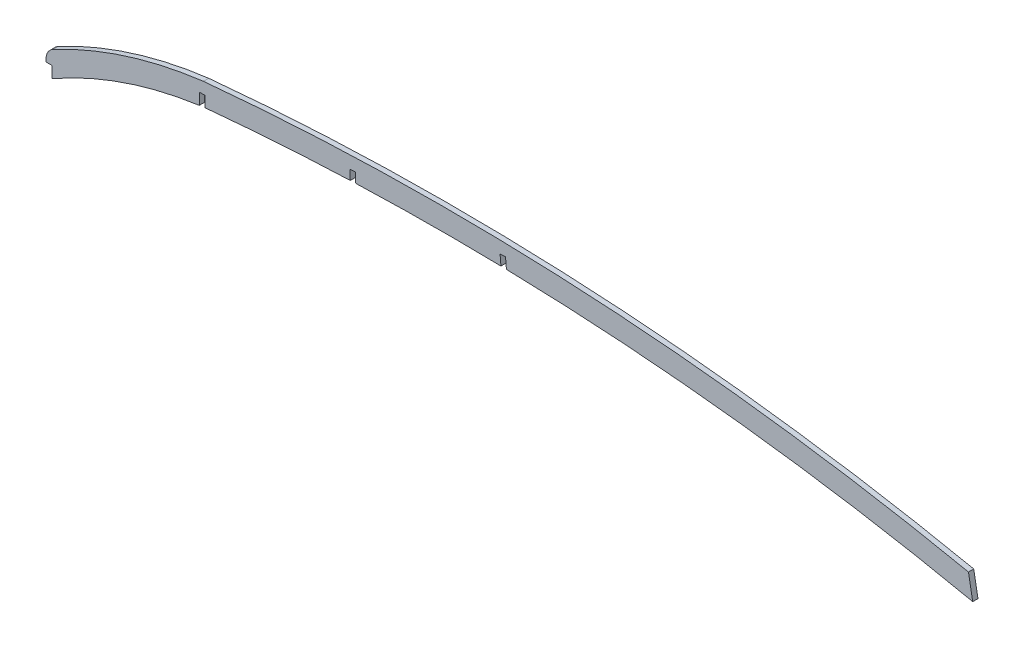
SolidWorks part; units mm, degrees
material "Balsa"
ref_plane "Front Plane" through (0, 0, 0) normal (0, 0, 1) x (1, 0, 0)
ref_plane "Top Plane" through (0, 0, 0) normal (0, 1, 0) x (1, 0, 0)
ref_plane "Right Plane" through (0, 0, 0) normal (1, 0, 0) x (0, 0, -1)
sketch "Sketch1" plane through (0, 0, 0) normal (0, 0, 1) x (1, 0, 0)
  line L0 (0, 101.6) -> (0, 100.0553)
  line L1 (0, -1.7463) -> (0, 1.7463) construction
  line L2 (0, 86.36) -> (8.1082, 86.36) construction
  line L3 (3.7499, 106.3536) -> (3.7499, -82.5359) construction
  line L4 (8.1082, 101.6) -> (0, 101.6) construction
  line L5 (92.329, 130.518) -> (92.329, 123.5672)
  line L6 (3.7499, 93.1973) -> (0, 91.0322) construction
  line L7 (0, 99.5163) -> (0, 88.039) construction
  line L8 (558.2295, 97.6273) -> (555.6382, 111.8229)
  line L9 (0, 91.0322) -> (0, 86.36) construction
  line L10 (3.7499, 93.1973) -> (3.7499, 100.0553)
  line L11 (3.7499, 100.0553) -> (0, 97.8902) construction
  line L12 (0, 97.8902) -> (0, 91.0322) construction
  line L13 (3.7499, 100.0553) -> (0, 100.0553)
  line L14 (0, 100.0553) -> (0, 97.8902) construction
  line L17 (92.3925, 137.6297) -> (92.3925, -54.5591) construction
  line L18 (95.631, 130.518) -> (95.631, 124.0109)
  line L19 (95.5675, -54.5591) -> (95.5675, 137.6297) construction
  line L20 (95.5675, 137.6297) -> (92.3925, 137.6297) construction
  line L21 (93.98, 137.6297) -> (93.98, 130.518) construction
  line L22 (92.329, 130.518) -> (95.631, 130.518)
  line L23 (92.329, 123.5672) -> (92.329, 122.506) construction
  line L24 (95.631, 124.0109) -> (95.631, 123.1918) construction
  line L25 (197.4984, -131.9724) -> (196.7865, -114.9693)
  line L26 (186.671, 126.627) -> (186.2782, 136.0069)
  line L27 (194.3262, -132.1052) -> (193.6143, -115.1021)
  line L28 (183.4987, 126.4942) -> (183.106, 135.8741)
  line L29 (193.6143, -115.1021) -> (196.7865, -114.9693)
  line L30 (186.671, 126.627) -> (183.4987, 126.4942)
  line L31 (194.3262, -132.1052) -> (197.4984, -131.9724)
  line L32 (183.106, 135.8741) -> (186.2782, 136.0069)
  line L33 (183.106, 135.8741) -> (186.2782, 136.0069) construction
  line L35 (186.671, 126.627) -> (183.4987, 126.4942) construction
  line L37 (183.4987, 126.4942) -> (183.106, 135.8741) construction
  line L39 (186.671, 126.627) -> (186.2782, 136.0069) construction
  line L41 (183.106, 135.8741) -> (186.671, 126.627) construction
  line L42 (184.8885, 131.2506) -> (184.9758, 129.1656) construction
  line L43 (183.294, 129.865) -> (183.0502, 135.6897)
  line L44 (186.5939, 129.9858) -> (186.3493, 135.8278)
  line L45 (183.0502, 135.6897) -> (186.3493, 135.8278)
  line L46 (183.2948, 129.8477) -> (183.294, 129.865) construction
  line L47 (276.7538, 136.7291) -> (273.5905, 136.4568)
  line L48 (298.3406, -114.0477) -> (295.1773, -114.32)
  line L49 (274.4392, 126.5971) -> (277.6025, 126.8694)
  line L50 (273.5905, 136.4568) -> (274.4392, 126.5971)
  line L51 (295.1773, -114.32) -> (296.6804, -131.7814)
  line L52 (276.7538, 136.7291) -> (277.6025, 126.8694)
  line L53 (298.3406, -114.0477) -> (299.8437, -131.5091)
  line L54 (296.6804, -131.7814) -> (299.8437, -131.5091)
  line L57 (276.7538, 136.7291) -> (277.6025, 126.8694) construction
  line L59 (273.5905, 136.4568) -> (274.4392, 126.5971) construction
  line L60 (274.4392, 126.5971) -> (277.6025, 126.8694) construction
  line L62 (276.7538, 136.7291) -> (273.5905, 136.4568) construction
  line L63 (274.4392, 126.5971) -> (276.7538, 136.7291) construction
  line L64 (275.5965, 131.6631) -> (274.3291, 146.3866) construction
  line L65 (274.0318, 130.5899) -> (273.5181, 136.5576)
  line L66 (277.3525, 130.5142) -> (276.8079, 136.8408)
  line L67 (273.5181, 136.5576) -> (276.8079, 136.8408)
  line L68 (274.0627, 130.231) -> (274.0318, 130.5899) construction
  arc A0 (4.3005, 108.7585) -> (94.8544, 137.376) centre (127, -121.92) cw
  arc A1 (4.3005, 108.7585) -> (0, 101.6) centre (8.1082, 101.6) ccw
  arc A2 (3.7499, 93.1973) -> (0, 86.36) centre (8.1082, 86.36) ccw construction
  arc A3 (94.8544, 137.376) -> (555.6382, 111.8229) centre (240.8652, -1397) cw
  arc A4 (3.7499, 93.1973) -> (92.329, 123.5672) centre (127, -121.92) cw
  arc A5 (96.3112, 124.0967) -> (183.294, 129.865) centre (240.8652, -1397) cw
  arc A6 (10.5733, 96.9655) -> (96.3112, 124.0967) centre (127, -121.92) cw construction
  arc A7 (94.4927, 137.3434) -> (3.7499, 106.3536) centre (112.883, -64.8553) ccw construction
  arc A8 (96.3112, 124.0967) -> (552.9103, 98.7469) centre (240.8652, -1397) cw construction
  arc A9 (4.3005, 108.7585) -> (94.8544, 137.376) centre (127, -121.92) cw construction
  arc A10 (92.329, 123.5672) -> (95.631, 124.0109) centre (127, -121.92) cw construction
  arc A11 (94.8544, 137.376) -> (555.6382, 111.8229) centre (240.8652, -1397) cw construction
  arc A12 (95.631, 124.0109) -> (96.3112, 124.0967) centre (127, -121.92) cw
  arc A13 (556.7512, 105.7321) -> (99.1899, 122.2822) centre (270.5046, -1474.7614) ccw construction
  arc A14 (183.294, 129.865) -> (183.3575, 129.8673) centre (240.8652, -1397) cw construction
  arc A15 (184.9439, 129.9263) -> (185.3927, 129.9426) centre (240.8652, -1397) cw construction
  arc A16 (183.3575, 129.8673) -> (184.9439, 129.9263) centre (240.8652, -1397) cw construction
  arc A17 (185.3927, 129.9426) -> (186.5304, 129.9835) centre (240.8652, -1397) cw construction
  arc A18 (186.5939, 129.9858) -> (274.0318, 130.5899) centre (240.8652, -1397) cw
  arc A19 (186.5304, 129.9835) -> (186.5939, 129.9858) centre (240.8652, -1397) cw construction
  arc A20 (274.0957, 130.5885) -> (275.3447, 130.5609) centre (240.8652, -1397) cw construction
  arc A21 (277.3525, 130.5142) -> (558.2295, 97.6273) centre (240.8652, -1397) cw
  arc A22 (274.0318, 130.5899) -> (274.0957, 130.5885) centre (240.8652, -1397) cw construction
  arc A23 (275.3447, 130.5609) -> (277.2887, 130.5157) centre (240.8652, -1397) cw construction
  arc A24 (277.2887, 130.5157) -> (277.3525, 130.5142) centre (240.8652, -1397) cw construction
  spline S0 degree 3 poles (981.3177, 1818.2675) (1139.722, 204.4849) (873.2182, 1.0169) (565.628, -88.9106) (559.2919, -90.7077) (-121.8164, -278.7114) (-929.5333, 36.0269) (-1233.6865, -867.5095) knots -11.664502 -11.664502 -11.664502 -11.664502 0.25 0.25 0.5 0.5 27.071012 27.071012 27.071012 27.071012 only from (590.8643, -81.3536) to (514.7143, -102.4537) construction
  spline S1 degree 3 poles (1062.5522, -1662.3274) (1783.386, 752.2598) (1192.007, 51.9761) (480.6823, -110.4688) (472.1454, -112.3347) (455.0337, -115.879) (446.4591, -117.5582) (433.5613, -119.8984) (429.2558, -120.648) (422.7903, -121.7356) (420.6337, -122.0915) (417.3979, -122.6188) (416.3191, -122.7935) (329.7173, -136.7537) (244.3749, -151.8452) (-150.7518, 1789.6158) knots -20.37019 -20.37019 -20.37019 -20.37019 0.25 0.25 0.5 0.5 0.75 0.75 0.875 0.875 0.9375 0.9375 0.96875 0.96875 3.445896 3.445896 3.445896 3.445896 only from (514.7143, -102.4537) to (412.003, -123.4859) construction
  spline S2 degree 3 poles (-1526.2092, 975.8893) (-966.7298, 244.4948) (-373.5074, -121.9571) (226.7788, -133.168) (266.5142, -132.8729) (279.7628, -132.6016) (299.6408, -131.9345) (306.2677, -131.6688) (319.5231, -131.0505) (326.1536, -130.6977) (943.6584, -93.7895) (1501.3881, 309.0053) (2017.121, 1001.2295) knots -5.168103 -5.168103 -5.168103 -5.168103 0.25 0.5 0.5 0.625 0.625 0.6875 0.6875 0.75 0.75 6.511417 6.511417 6.511417 6.511417 only from (94.4926, -125.8525) to (412.003, -123.4859) construction
  spline S3 degree 3 poles (82.8406, 1879.826) (-241.5287, 509.6599) (-195.4311, -0.6421) (32.0968, -110.0953) (39.5136, -113.1375) (50.922, -117.0433) (54.7721, -118.2354) (60.6197, -119.8556) (62.5829, -120.3681) (66.5243, -121.3341) (68.5001, -121.787) (343.1899, -180.4478) (711.1357, 326.3263) (1193.75, 1513.3939) knots -7.368418 -7.368418 -7.368418 -7.368418 0.25 0.25 0.5 0.5 0.625 0.625 0.6875 0.6875 0.75 0.75 9.354609 9.354609 9.354609 9.354609 only from (3.7499, -94.8626) to (94.4926, -125.8525) construction
  spline S6 degree 3 poles (590.8643, -81.3536) (584.5771, -83.3154) (578.2709, -85.2143) (565.628, -88.9106) (559.2919, -90.7077) (540.2459, -95.9648) (527.5015, -99.2922) (514.7143, -102.4537) knots 0 0 0 0 0.25 0.25 0.5 0.5 1 1 1 1 construction
  spline S7 degree 3 poles (514.7143, -102.4537) (506.2284, -104.5517) (497.724, -106.577) (480.6823, -110.4688) (472.1454, -112.3347) (455.0337, -115.879) (446.4591, -117.5582) (433.5613, -119.8984) (429.2558, -120.648) (422.7903, -121.7356) (420.6337, -122.0915) (417.3979, -122.6188) (416.3191, -122.7935) (414.1613, -123.1413) (413.0825, -123.3155) (412.003, -123.4859) knots 0 0 0 0 0.25 0.25 0.5 0.5 0.75 0.75 0.875 0.875 0.9375 0.9375 0.96875 0.96875 1 1 1 1 construction
  spline S8 degree 3 poles (94.4926, -125.8525) (120.9278, -128.4258) (173.8258, -132.179) (226.7788, -133.168) (266.5142, -132.8729) (279.7628, -132.6016) (299.6408, -131.9345) (306.2677, -131.6688) (319.5231, -131.0505) (326.1536, -130.6977) (359.2877, -128.7173) (385.6949, -126.4433) (412.003, -123.4859) knots 0 0 0 0 0.25 0.5 0.5 0.625 0.625 0.6875 0.6875 0.75 0.75 1 1 1 1 construction
  spline S9 degree 3 poles (3.7499, -94.8626) (10.597, -99.2271) (17.6385, -103.1401) (32.0968, -110.0953) (39.5136, -113.1375) (50.922, -117.0433) (54.7721, -118.2354) (60.6197, -119.8556) (62.5829, -120.3681) (66.5243, -121.3341) (68.5001, -121.787) (78.4043, -123.9021) (86.408, -125.1172) (94.4926, -125.8525) knots 0 0 0 0 0.25 0.25 0.5 0.5 0.625 0.625 0.6875 0.6875 0.75 0.75 1 1 1 1 construction
  spline S15 degree 3 poles (587.4426, -62.5747) (587.1827, -61.1511) (586.6535, -58.2526) (585.7873, -53.5174) (584.8512, -48.394) (583.8406, -42.8532) (582.7565, -36.9006) (581.5991, -30.5376) (580.1295, -22.4773) (578.3524, -12.6853) (576.2505, -1.1976) (574.1192, 10.4518) (571.9272, 22.5233) (569.819, 34.0829) (567.7342, 45.5019) (565.8232, 55.9911) (564.3841, 63.8754) (563.4512, 68.9947) (562.9209, 71.9076) (562.4102, 74.7138) (561.9192, 77.4122) (561.4478, 80.0018) (560.9959, 82.4822) (560.5637, 84.8528) (560.1512, 87.1138) (559.7582, 89.2651) (559.385, 91.3073) (559.0312, 93.2414) (558.6975, 95.0661) (558.3822, 96.7905) (558.1867, 97.8615) (558.0896, 98.3936) knots 0 0 0 0 0.031687 0.064515 0.098497 0.133644 0.169967 0.207478 0.246191 0.30842 0.370332 0.432609 0.495165 0.563925 0.620591 0.686243 0.746551 0.766006 0.785258 0.804303 0.823142 0.841774 0.860197 0.878411 0.896416 0.91421 0.931793 0.949164 0.966322 0.983268 1 1 1 1 construction
  point P53 (93.98, 130.518)
  dimension "D4" = 8.1082
  dimension "D2" = 127
  dimension "D8" = 1397
  dimension "D9" = 30
  dimension "D1" = 15.24
  dimension "D3" = 8.1082
  dimension "D5" = 8.1082
  dimension "D6" = 101.6
  dimension "D7" = 121.92
  dimension "D10" = 6.858
  dimension "D11" = 3.7499
  dimension "D12" = 3.302
  dimension "D13" = 6.858
  dimension "D14" = 3.302
  dimension "D15" = 5.842
  dimension "D16" = 3.302
  dimension "D17" = 6.35
extrude "Boss-Extrude1" add sketch "Sketch1" along normal mid plane 3.175
equation "\"slotwidth\"=0.167708"
